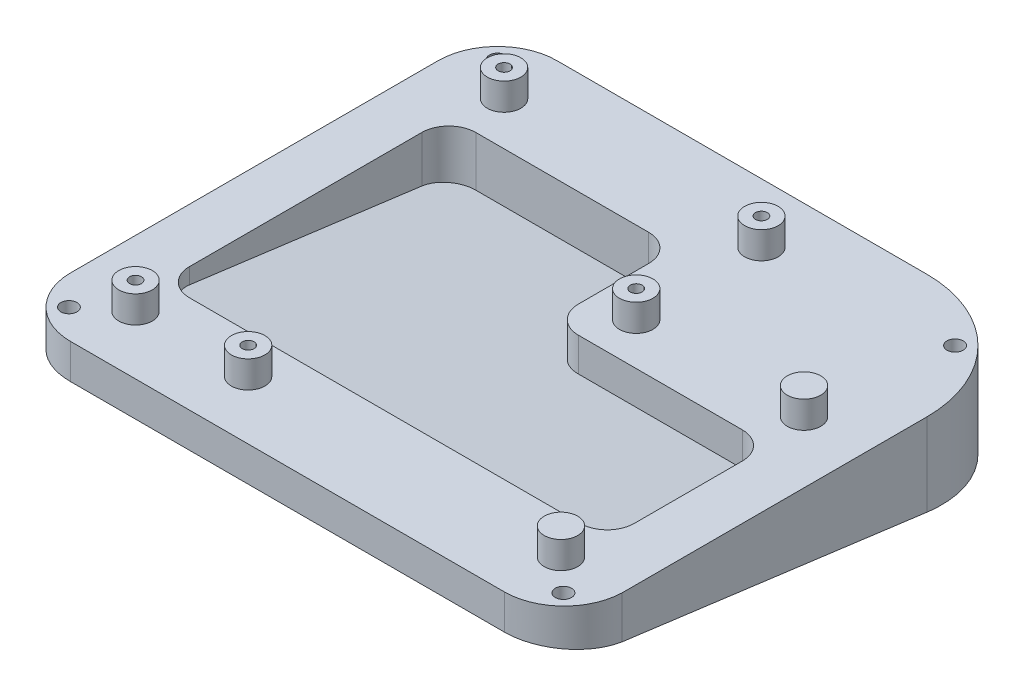
SolidWorks part; units mm, degrees
material "PMMA"
ref_plane "Front Plane" through (0, 0, 0) normal (0, 0, 1) x (1, 0, 0)
ref_plane "Top Plane" through (0, 0, 0) normal (0, 1, 0) x (1, 0, 0)
ref_plane "Right Plane" through (0, 0, 0) normal (1, 0, 0) x (0, 0, -1)
sketch "Sketch1" plane through (0, 0, 0) normal (0, 1, 0) x (1, 0, 0)
  line L1 (-51.2097, -0.298) -> (51.1203, -0.298) construction
  line L17 (-40.2097, 44.712) -> (28.2403, 44.712)
  line L18 (51.1203, 21.832) -> (51.1203, -34.5982)
  line L19 (-40.2097, -45.308) -> (40.1303, -45.308)
  line L20 (-51.2097, 33.712) -> (-51.2097, -34.308)
  line L22 (-42.3087, 35.8109) -> (-47.9879, 41.4901) construction
  line L23 (38.7844, 32.3761) -> (44.4189, 38.0106) construction
  line L24 (47.7767, -42.1608) -> (44.6541, -38.9206) construction
  line L25 (-47.9879, -42.0862) -> (-42.2863, -36.4294) construction
  circle A1 centre (-39.0197, -34.478) radius 1.1
  circle A2 centre (-18.1797, -34.478) radius 1.1
  circle A3 centre (-39.0197, 33.732) radius 1.1
  circle A4 centre (8.6103, 33.7319) radius 1.1
  circle A5 centre (8.655, 10.512) radius 1.1
  arc A22 (51.1203, 21.832) -> (28.2403, 44.712) centre (28.2403, 21.832) ccw
  arc A23 (51.1203, -34.5982) -> (40.1303, -45.308) centre (40.0369, -34.2185) cw
  arc A24 (-51.2097, -34.308) -> (-40.2097, -45.308) centre (-40.2097, -34.308) ccw
  arc A25 (-40.2097, 44.712) -> (-51.2097, 33.712) centre (-40.2097, 33.712) ccw
  circle A28 centre (-45.8666, 39.3688) radius 1.5
  circle A29 centre (42.2975, 35.8892) radius 1.5
  circle A30 centre (45.695, -40.0007) radius 1.5
  circle A31 centre (-45.8583, -39.9733) radius 1.5
  point P0 (0, 0)
  point P36 (43.165, -37.128)
  dimension "D4" = 2.2
  dimension "D41" = 3
  dimension "D43" = 3
  dimension "D45" = 3
  dimension "D47" = 3
  dimension "D2" = 10.83
  dimension "D3" = 20.84
  dimension "D5" = 12.19
  dimension "D6" = 12.19
  dimension "D7" = 10.98
  dimension "D9" = 47.63
  dimension "D10" = 23.22
  dimension "D40" = 3
  dimension "D42" = 3
  dimension "D44" = 3
  dimension "D46" = 3
extrude "Boss-Extrude1" add sketch "Sketch1" along normal blind 3.048
sketch "Sketch2" plane through (0, 3.048, 0) normal (0, 1, 0) x (1, 0, 0)
  line L0 (-39.0197, -34.478) -> (39.7203, -34.478) construction
  line L1 (8.655, 10.512) -> (39.7203, 10.512) construction
  circle A0 centre (-39.0197, -34.478) radius 1.1 construction
  circle A1 centre (-18.1797, -34.478) radius 1.1 construction
  circle A2 centre (8.655, 10.512) radius 1.1 construction
  circle A3 centre (8.6103, 33.7319) radius 1.1 construction
  circle A4 centre (-39.0197, 33.732) radius 1.1 construction
  circle A5 centre (-39.0197, -34.478) radius 1.1
  circle A6 centre (-18.1797, -34.478) radius 1.1
  circle A7 centre (8.655, 10.512) radius 1.1
  circle A8 centre (8.6103, 33.7319) radius 1.1
  circle A9 centre (-39.0197, 33.732) radius 1.1
  circle A10 centre (-39.0197, 33.732) radius 3.1
  circle A11 centre (8.6103, 33.7319) radius 3.1
  circle A12 centre (8.655, 10.512) radius 3.1
  circle A13 centre (-18.1797, -34.478) radius 3.1
  circle A14 centre (-39.0197, -34.478) radius 3.1
  circle A15 centre (39.7203, -34.478) radius 3.1
  circle A16 centre (39.7203, 10.512) radius 3.1
  dimension "D2" = 78.74
  dimension "D1" = 2
extrude "Boss-Extrude2" add sketch "Sketch2" along normal blind 5
extrude "Boss-Extrude4" add sketch "Sketch1<5>" against normal blind 13.75
sketch "Sketch1<5>" plane through (0, 0, 0) normal (0, 1, 0) x (1, 0, 0) same geometry as "Sketch1"
sketch "Sketch3" plane through (-51.2097, 0, 0) normal (-1, 0, 0) x (0, 0, 1)
  line L0 (-44.712, -13.75) -> (-33.712, -13.75) construction
  line L1 (-33.712, -13.75) -> (34.308, -13.75) construction
  line L2 (34.308, -13.75) -> (45.308, -13.75) construction
  line L3 (45.308, 3.048) -> (45.308, -13.75) construction
  line L5 (-44.712, -13.75) -> (-33.712, -13.75)
  line L6 (-33.712, -13.75) -> (34.308, -13.75)
  line L7 (34.308, -13.75) -> (45.308, -13.75)
  line L8 (45.308, -1.8986) -> (45.308, -13.75)
  line L10 (-44.712, -13.75) -> (45.308, -1.8986)
  dimension "D1" = 7.5
extrude "Cut-Extrude1" cut sketch "Sketch3" against normal through all
sketch "Sketch4" plane through (0, 3.048, 0) normal (0, 1, 0) x (1, 0, 0)
  line L0 (-40.2097, -45.308) -> (40.1303, -45.308) construction
  line L1 (0.7903, 2.692) -> (41.1203, 2.692)
  line L2 (-41.2097, 2.692) -> (-41.2097, -27.308)
  line L3 (-41.2097, -27.308) -> (41.1203, -27.308)
  line L4 (41.1203, 2.692) -> (41.1203, -27.308)
  line L5 (51.1203, -34.5982) -> (51.1203, 21.832) construction
  line L6 (-51.2097, 33.712) -> (-51.2097, -34.308) construction
  line L7 (-41.2097, 2.692) -> (-41.2097, 25.692)
  line L8 (-41.2097, 25.692) -> (0.7903, 25.692)
  line L10 (0.7903, 25.692) -> (0.7903, 2.692)
  dimension "D1" = 18
  dimension "D2" = 30
  dimension "D3" = 10
  dimension "D4" = 10
  dimension "D5" = 23
  dimension "D6" = 42
extrude "Cut-Extrude2" cut sketch "Sketch4" against normal offset from surface (6.2228 mm away) 5 up to face at (-39.0197, -3.4693, 33.378)
fillet "Fillet1" radius 5 6 edges at (41.1203, 1.9114, 27.308) (-41.2097, 1.9114, 27.308) (-41.2097, -1.5774, -25.692) (0.7903, -1.5774, -25.692) (41.1203, -0.0634, -2.692) (0.7903, -0.0634, -2.692)
sketch "Sketch5" plane through (0, -7.7296, 1.0176) normal (0, -0.9914, 0.1305) x (1, 0, 0)
  line L0 (-51.2097, 33.5777) -> (-51.2097, -35.0293) construction
  line L1 (40.1303, 44.6726) -> (-40.2097, 44.6726) construction
  line L2 (51.1203, 33.8703) -> (51.1203, -23.0467) construction
  line L3 (28.2403, -46.1242) -> (-40.2097, -46.1242) construction
  line L4 (-51.2097, 33.5777) -> (-51.2097, -35.0293)
  line L5 (40.1303, 44.6726) -> (-40.2097, 44.6726)
  line L6 (51.1203, 33.8703) -> (51.1203, -23.0467)
  line L7 (28.2403, -46.1242) -> (-40.2097, -46.1242)
  ellipse E0 centre (-40.2097, -35.0293) end of major axis (-40.2097, -46.1242) minor radius 11 (-51.2097, -35.0293) -> (-40.2097, -46.1242) ccw construction
  ellipse E1 centre (-40.2097, 33.5777) end of major axis (-40.2097, 22.4828) minor radius 11 (-40.2097, 44.6726) -> (-51.2097, 33.5777) ccw construction
  ellipse E2 centre (40.0369, 33.4874) end of major axis (40.0369, 22.3018) minor radius 11.0899 (51.1203, 33.8703) -> (40.1303, 44.6726) ccw construction
  ellipse E3 centre (28.2403, -23.0467) end of major axis (28.2403, 0.0307) minor radius 22.88 (28.2403, -46.1242) -> (51.1203, -23.0467) ccw construction
  ellipse E4 centre (-40.2097, -35.0293) end of major axis (-40.2097, -46.1242) minor radius 11 (-51.2097, -35.0293) -> (-40.2097, -46.1242) ccw
  ellipse E5 centre (-40.2097, 33.5777) end of major axis (-40.2097, 22.4828) minor radius 11 (-40.2097, 44.6726) -> (-51.2097, 33.5777) ccw
  ellipse E6 centre (40.0369, 33.4874) end of major axis (40.0369, 22.3018) minor radius 11.0899 (51.1203, 33.8703) -> (40.1303, 44.6726) ccw
  ellipse E7 centre (28.2403, -23.0467) end of major axis (28.2403, -46.1242) minor radius 22.88 (28.2403, -46.1242) -> (51.1203, -23.0467) ccw
extrude "Boss-Extrude6" add sketch "Sketch5" along direction (0, -1, 0) on the side of the normal blind 1.5
